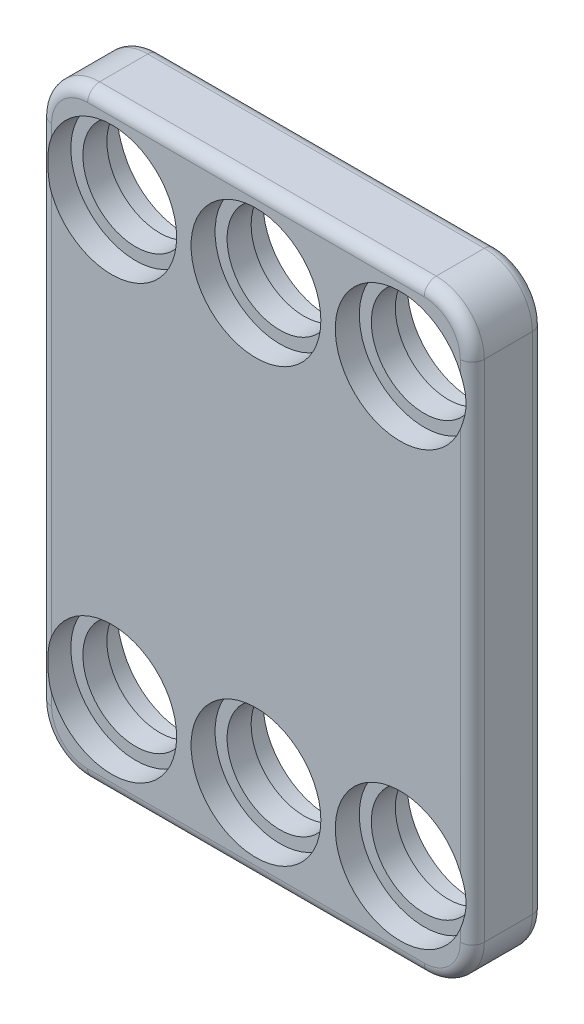
SolidWorks part; units mm, degrees
material "ABS"
ref_plane "Front Plane" through (0, 0, 0) normal (0, 0, 1) x (1, 0, 0)
ref_plane "Top Plane" through (0, 0, 0) normal (0, 1, 0) x (1, 0, 0)
ref_plane "Right Plane" through (0, 0, 0) normal (1, 0, 0) x (0, 0, -1)
sketch "Sketch1" plane through (0, 0, 0) normal (0, 0, 1) x (1, 0, 0)
  line L1 (9, 3.5) -> (-9, 3.5)
  line L2 (9, 3.5) -> (9, -21.5)
  line L3 (9, -21.5) -> (-9, -21.5)
  line L4 (-9, 3.5) -> (-9, -21.5)
  point P6 (6, 0)
  point P7 (0, 0)
  point P8 (-6, 0)
  point P9 (6, -18)
  point P10 (0, -18)
  point P11 (-6, -18)
extrude "Boss-Extrude1" add sketch "Sketch1" along normal blind 3
hole_wizard "Hole1" positions "Sketch5" profile "Sketch4" legacy
sketch "Sketch5" plane through (0, 0, 3) normal (0, 0, 1) x (1, 0, 0)
  point P0 (-6, 0)
  point P3 (0, 0)
  point P6 (6, 0)
  point P9 (-6, -18)
  point P12 (0, -18)
  point P15 (6, -18)
sketch "Sketch4" plane through (-6, 0, 3) normal (1, 0, 0) x (0, -1, 0)
  line L0 (0, 0) -> (0, 100)
  line L1 (0, 100) -> (2.2, 100)
  line L2 (2.2, 100) -> (2.2, 1)
  line L3 (2.2, 1) -> (2.7, 1)
  line L4 (2.7, 1) -> (2.7, 0)
  line L5 (2.7, 0) -> (0, 0)
  line L6 (0, 110) -> (0, -10) construction
  dimension "Diameter" = 4.4
  dimension "Depth" = 100
  dimension "C-Bore Diameter" = 5.4
  dimension "C-Bore Depth" = 1
hole_wizard "Hole2" positions "Sketch7" profile "Sketch6" legacy
sketch "Sketch7" plane through (0, 0, 0) normal (0, 0, -1) x (-1, 0, 0)
  point P0 (-6, 0)
  point P3 (0, 0)
  point P6 (6, 0)
  point P9 (6, -18)
  point P12 (0, -18)
  point P15 (-6, -18)
sketch "Sketch6" plane through (6, 0, 0) normal (1, 0, 0) x (0, 1, 0)
  line L0 (0, 0) -> (0, 100)
  line L1 (0, 100) -> (2.2, 100)
  line L2 (2.2, 100) -> (2.2, 1)
  line L3 (2.2, 1) -> (2.7, 1)
  line L4 (2.7, 1) -> (2.7, 0)
  line L5 (2.7, 0) -> (0, 0)
  line L6 (0, 110) -> (0, -10) construction
  dimension "Diameter" = 4.4
  dimension "Depth" = 100
  dimension "C-Bore Diameter" = 5.4
  dimension "C-Bore Depth" = 1
fillet "Fillet1" radius 2 4 edges at (9, -21.5, 1.5) (-9, -21.5, 1.5) (-9, 3.5, 1.5) (9, 3.5, 1.5)
fillet "Fillet2" radius 0.5 16 edges at (8.4142, -20.9142, 3) (0, -21.5, 3) (-8.4142, -20.9142, 3) (-9, -9, 3) (-8.4142, 2.9142, 3) (0, 3.5, 3) (8.4142, 2.9142, 3) (8.4142, -20.9142, 0) (0, -21.5, 0) (-8.4142, -20.9142, 0) (-9, -9, 0) (-8.4142, 2.9142, 0) (0, 3.5, 0) (8.4142, 2.9142, 0) (9, -9, 3) (9, -9, 0)
